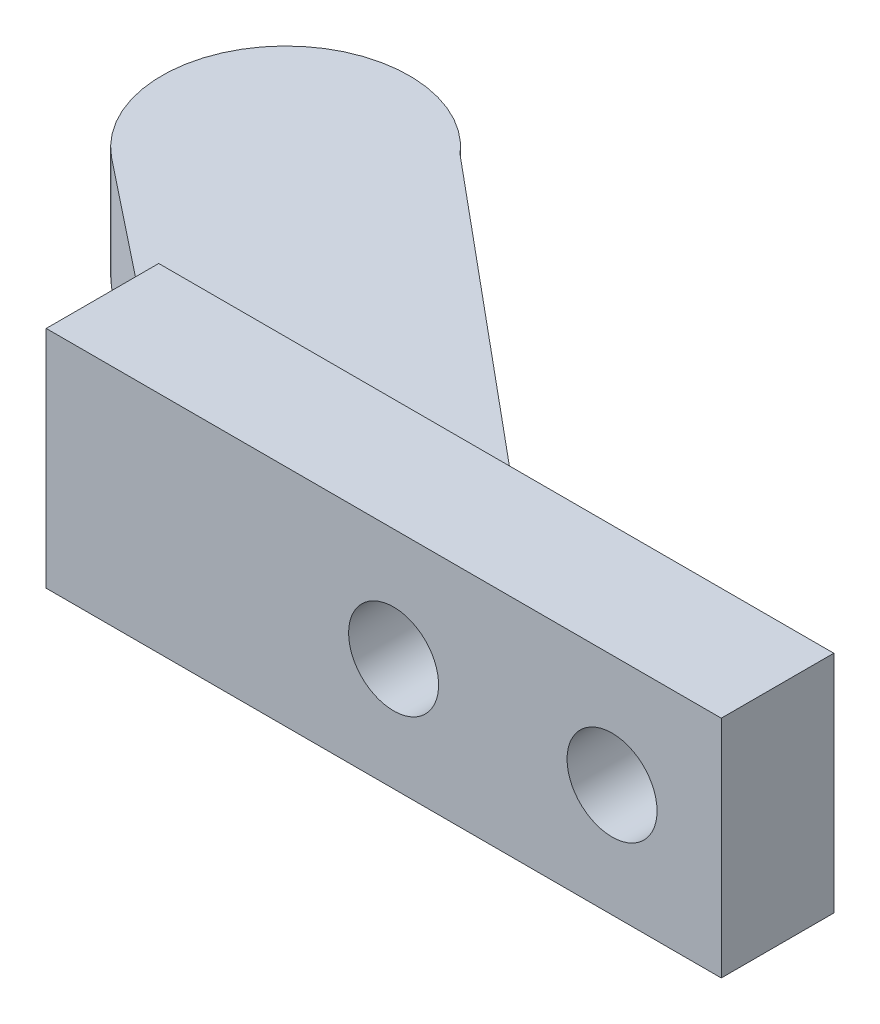
SolidWorks part; units mm, degrees
ref_plane "Front Plane" through (0, 0, 0) normal (0, 0, 1) x (1, 0, 0)
ref_plane "Top Plane" through (0, 0, 0) normal (0, 1, 0) x (1, 0, 0)
ref_plane "Right Plane" through (0, 0, 0) normal (1, 0, 0) x (0, 0, -1)
sketch "Sketch1" plane through (0, 0, 0) normal (0, 1, 0) x (1, 0, 0)
  line L0 (21.854, -19.9533) -> (21.854, -14.9533)
  line L1 (21.854, -14.9533) -> (2.4374, -14.9533)
  line L4 (-8.146, -19.9533) -> (21.854, -19.9533)
  line L5 (-14.8074, -8.6533) -> (-14.8074, -7.6533)
  line L6 (2.4374, -14.9533) -> (21.854, -14.9533)
  line L9 (21.854, -14.9533) -> (21.854, -16.9533)
  line L10 (2.4374, -14.9533) -> (-10.6321, -4.0731)
  line L11 (-18.268, -11.9281) -> (-8.146, -19.9533)
  arc A0 (-10.6321, -4.0731) -> (-18.268, -11.9281) centre (-14.8074, -7.6533) ccw
  circle A1 centre (-14.8074, -7.6533) radius 2.6
extrude "Boss-Extrude1" add sketch "Sketch1" along normal blind 5 contours A0 L4 L0 A1 | A1 region at (-2.4033, 0, 13.8039) region at (-17.3338, 0, 7.6533)
extrude "Boss-Extrude2" add sketch "Sketch1<3>" against normal blind 5 contours A1 region at (-17.3338, 0, 7.6533)
sketch "Sketch1<3>" plane through (0, 0, 0) normal (0, 1, 0) x (1, 0, 0) same geometry as "Sketch1"
chamfer "Chamfer1" distance 0.5 angle 45 1 edges at (-14.8074, -5, 10.2533)
extrude "Boss-Extrude3" add sketch "Sketch1<4>" along normal blind 5 contours L0 L1 region at (-2.4033, 0, 13.8039)
sketch "Sketch1<4>" plane through (0, 0, 0) normal (0, 1, 0) x (1, 0, 0) same geometry as "Sketch1"
sketch "Sketch5" plane through (0, 5, 0) normal (0, 1, 0) x (1, 0, 0)
  line L0 (-8.146, -14.9533) -> (-14.4524, -14.9533)
  line L1 (21.854, -14.9533) -> (-8.146, -14.9533)
  line L2 (21.854, -14.9533) -> (21.854, -19.9533)
  line L3 (21.854, -19.9533) -> (-8.146, -19.9533)
  line L5 (-18.268, -11.9281) -> (-8.146, -19.9533) construction
  line L6 (-14.4524, -14.9533) -> (-8.146, -19.9533)
extrude "Boss-Extrude5" add sketch "Sketch5" along normal blind 5
fillet "Fillet1" radius 1 1 edges at (-14.8074, 0, 10.2533)
sketch "Sketch7" plane through (0, 10, 0) normal (0, 1, 0) x (1, 0, 0)
  line L0 (21.854, -19.9533) -> (21.854, -24.9533)
  line L1 (21.854, -24.9533) -> (-6.6349, -24.9533)
  line L2 (-14.4524, -14.9533) -> (-8.146, -19.9533)
  line L3 (-8.146, -19.9533) -> (-14.4524, -14.9533)
  line L4 (-8.146, -19.9533) -> (-8.146, -24.9533)
  line L5 (-8.146, -24.9533) -> (-6.6349, -24.9533)
  line L6 (-8.146, -19.9533) -> (21.854, -19.9533)
  line M4 (-8.146, -19.9533) -> (21.854, -19.9533)
extrude "Boss-Extrude6" add sketch "Sketch7" against normal blind 10 contours L4 L5 L1 L0 M4 region at (6.854, 10, 22.4533)
sketch "Sketch6" plane through (0, 0, 14.9533) normal (0, 0, -1) x (-1, 0, 0)
  line L0 (-12.1457, 0) -> (-12.1457, 10)
  line L1 (-21.854, 0) -> (-2.4374, 0) construction
  line L2 (-21.854, 10) -> (14.4524, 10) construction
  line L3 (-12.1457, 5) -> (-2.4374, 5)
  circle A0 centre (-7.2916, 5) radius 2
  circle A1 centre (-16.9999, 5) radius 2
extrude "Cut-Extrude2" cut sketch "Sketch6" against normal through all contours A0 | A1
sketch "Sketch8" plane through (0, 0, 14.9533) normal (0, 0, -1) x (-1, 0, 0)
  line L6 (-21.854, 0) -> (-2.4374, 0)
  line L7 (-2.4374, 0) -> (-2.4374, 5)
  line L8 (-2.4374, 5) -> (14.4524, 5)
  line L9 (14.4524, 5) -> (14.4524, 10)
  line L10 (14.4524, 10) -> (-21.854, 10)
  line L11 (-21.854, 10) -> (-21.854, 0)
  line L12 (-21.854, 0) -> (-2.4374, 0)
  line L13 (-2.4374, 0) -> (-2.4374, 5)
  line L14 (-2.4374, 5) -> (14.4524, 5)
  line L15 (14.4524, 5) -> (14.4524, 10)
  line L16 (14.4524, 10) -> (-21.854, 10)
  line L17 (-21.854, 10) -> (-21.854, 0)
  dimension "D1" = 0
extrude "Cut-Extrude3" cut sketch "Sketch8" against normal blind 5
fillet "Fillet2" radius 2 1 edges at (-2.8543, 5, 19.9533)
